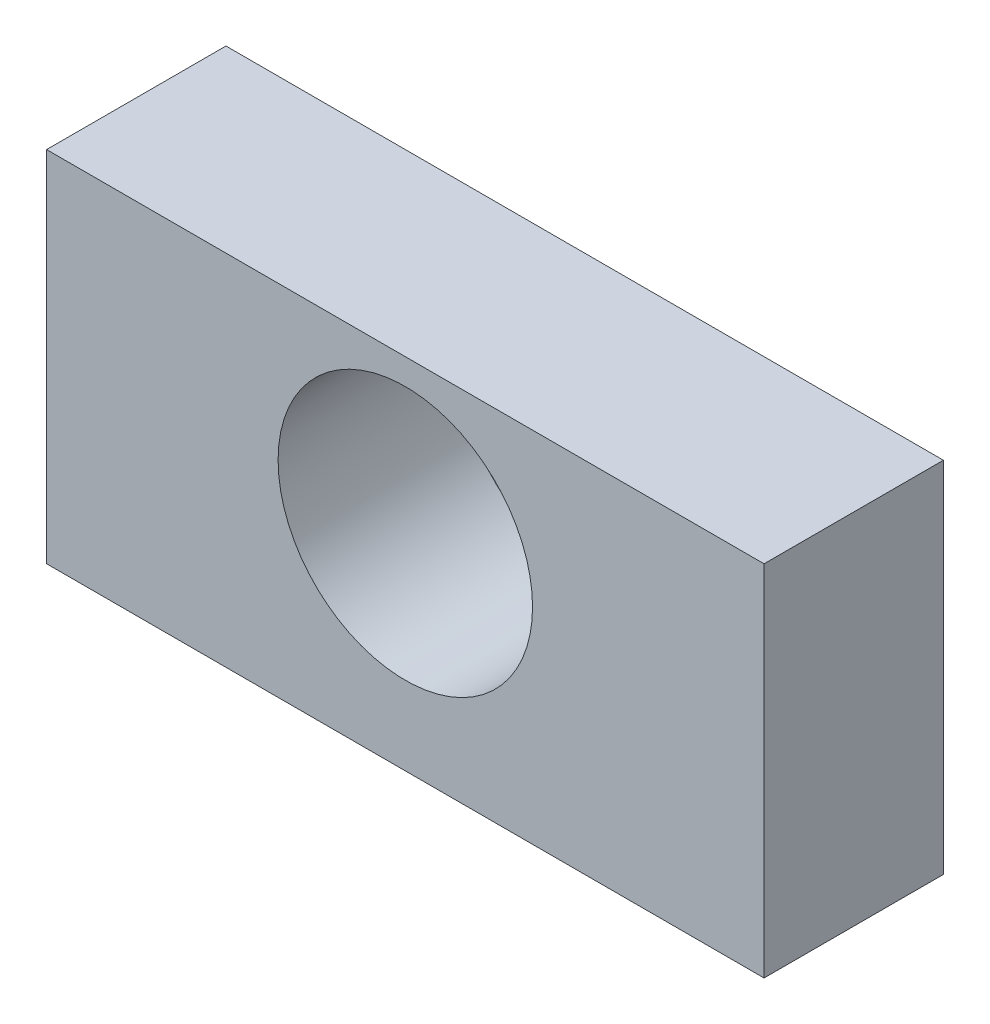
SolidWorks part; units mm, degrees
ref_plane "Front Plane" through (0, 0, 0) normal (0, 0, 1) x (1, 0, 0)
ref_plane "Top Plane" through (0, 0, 0) normal (0, 1, 0) x (1, 0, 0)
ref_plane "Right Plane" through (0, 0, 0) normal (1, 0, 0) x (0, 0, -1)
sketch "Sketch1" plane through (0, 0, 0) normal (0, 0, 1) x (1, 0, 0)
  line L1 (-9.525, -4.7625) -> (9.525, -4.7625)
  line L2 (-9.525, -4.7625) -> (-9.525, 4.7625)
  line L3 (-9.525, 4.7625) -> (9.525, 4.7625)
  line L4 (9.525, -4.7625) -> (9.525, 4.7625)
  line L5 (-9.525, -4.7625) -> (9.525, 4.7625) construction
  line L6 (-9.525, 4.7625) -> (9.525, -4.7625) construction
  point P0 (0, 0)
  dimension "D1" = 19.05
  dimension "D2" = 9.525
extrude "Extrude1" add sketch "Sketch1" along normal blind 4.7625
sketch "Sketch2" plane through (0, 0, 4.7625) normal (0, 0, 1) x (1, 0, 0)
  line L0 (0, 4.7625) -> (0, 0.6985) construction
  line L1 (9.525, 4.7625) -> (-9.525, 4.7625) construction
  dimension "D1" = 4.064
hole_wizard "1/4 Clearance Hole1" positions "3DSketch2" profile "Sketch4" hole size "1/4" standard "Ansi Inch"
sketch3d "3DSketch2"
  point P2 (0, 0.6985, 4.7625)
sketch "Sketch4" plane through (0, 0.6985, 4.7625) normal (1, 0, 0) x (0, -1, 0)
  line L0 (0, 0) -> (0, 17.2698)
  line L1 (0, 17.2698) -> (3.3782, 15.24)
  line L2 (3.3782, 15.24) -> (3.3782, 0)
  line L5 (3.3782, 0) -> (0, 0)
  line L10 (0, 17.2698) -> (-3.3782, 15.24) construction
  line L11 (0, -6.35) -> (0, 107.95) construction
  dimension "Hole Dia." = 6.7564
  dimension "Hole Depth" = 15.24
  dimension "Drill Angle" = 118
